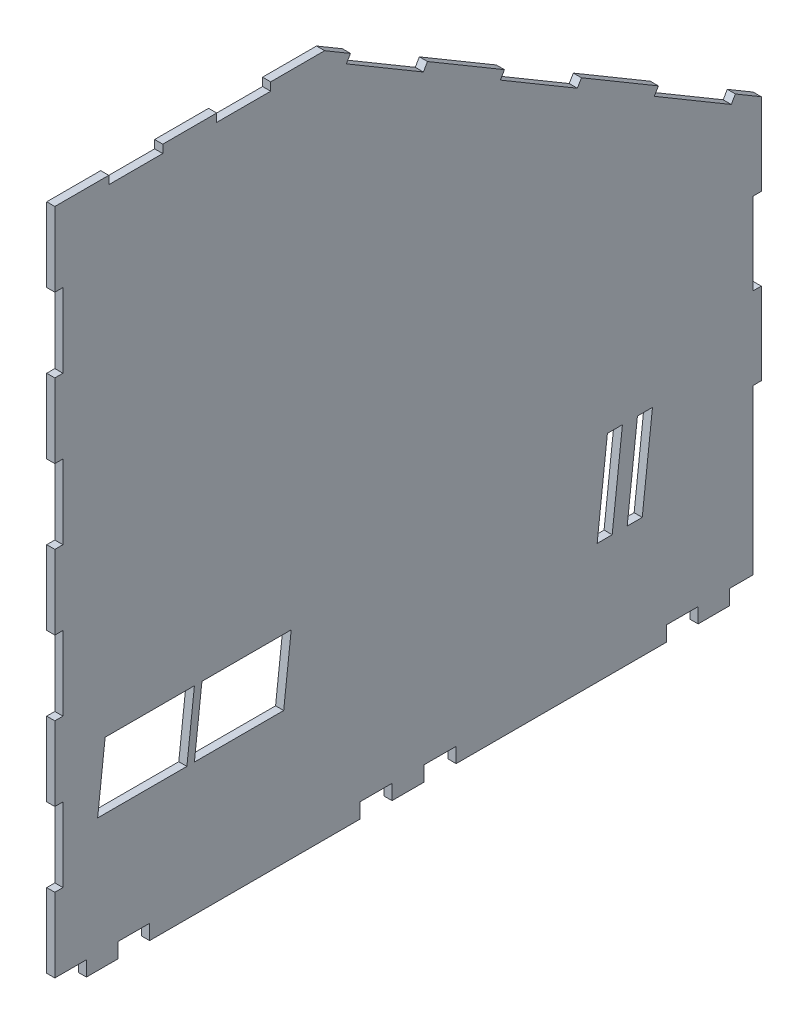
SolidWorks part; units mm, degrees
ref_plane "Ön Düzlem" through (0, 0, 0) normal (0, 0, 1) x (1, 0, 0)
ref_plane "Üst Düzlem" through (0, 0, 0) normal (0, 1, 0) x (1, 0, 0)
ref_plane "Sağ Düzlem" through (0, 0, 0) normal (1, 0, 0) x (0, 0, -1)
sketch "Sketch1" plane through (0, 0, 0) normal (1, 0, 0) x (0, 0, -1)
  line L11 (117.52, -0.68) -> (117.52, 26.6)
  line L96 (71.32, -44.8) -> (66.32, -44.8)
  line L97 (62.9109, -74.8) -> (66.32, -44.8)
  line L98 (67.9109, -74.8) -> (71.32, -44.8)
  line L99 (72.9109, -74.8) -> (76.32, -44.8)
  line L100 (77.9109, -74.8) -> (81.32, -44.8)
  line L101 (76.32, -44.8) -> (81.32, -44.8)
  line L102 (-68.58, -48.8) -> (-41.38, -48.8)
  line L103 (-71.08, -70.8) -> (-41.38, -70.8)
  line L104 (-100.78, -48.8) -> (-103.28, -70.8)
  line L105 (-100.78, -70.8) -> (-103.28, -70.8)
  line L106 (-38.88, -48.8) -> (-41.38, -70.8)
  line L107 (-41.38, -48.8) -> (-38.88, -48.8)
  line L108 (-71.08, -48.8) -> (-73.58, -70.8)
  line L109 (-68.58, -48.8) -> (-71.08, -70.8)
  line L110 (-100.78, -70.8) -> (-73.58, -70.8)
  line L111 (-100.78, -48.8) -> (-71.08, -48.8)
  line L112 (62.9109, -74.8) -> (67.9109, -74.8)
  line L113 (77.9109, -74.8) -> (72.9109, -74.8)
  line L114 (114.82, -82.52) -> (114.82, -109.8)
  line L115 (-81.612, 112.5) -> (-63.658, 112.5)
  line L116 (-45.704, 112.5) -> (-27.75, 112.5)
  line L117 (81.9271, 44.5098) -> (83.3014, 46.8339)
  line L118 (56.3162, 59.6539) -> (57.6905, 61.978)
  line L119 (30.7053, 74.7979) -> (32.0795, 77.122)
  line L120 (5.0944, 89.942) -> (-20.5165, 105.086)
  line L121 (56.3162, 59.6539) -> (30.7053, 74.7979)
  line L122 (-19.1423, 107.4101) -> (-20.5165, 105.086)
  line L123 (108.9123, 31.6899) -> (107.538, 29.3658)
  line L124 (-86, -114.8) -> (-86, -112.5)
  line L125 (-16, -114.8) -> (-86, -114.8)
  line L126 (-99.566, 109.8) -> (-99.566, 112.5)
  line L127 (-81.612, 109.8) -> (-81.612, 112.5)
  line L128 (-63.658, 109.8) -> (-63.658, 112.5)
  line L129 (-45.704, 109.8) -> (-45.704, 112.5)
  line L130 (108.9123, 31.6899) -> (117.52, 26.6)
  line L131 (-63.658, 109.8) -> (-45.704, 109.8)
  line L132 (-16, -112.5) -> (-16, -114.8)
  line L133 (-99.566, 109.8) -> (-81.612, 109.8)
  line L134 (16, -114.8) -> (16, -112.5)
  line L135 (107.538, 29.3658) -> (81.9271, 44.5098)
  line L136 (5.0944, 89.942) -> (6.4686, 92.2661)
  line L137 (57.6905, 61.978) -> (83.3014, 46.8339)
  line L138 (-117.52, -60.4) -> (-114.82, -60.4)
  line L139 (-117.52, -35.7) -> (-114.82, -35.7)
  line L140 (-117.52, -11) -> (-114.82, -11)
  line L141 (-117.52, 38.4) -> (-114.82, 38.4)
  line L142 (-117.52, 63.1) -> (-114.82, 63.1)
  line L143 (-117.52, 87.8) -> (-114.82, 87.8)
  line L144 (-117.52, 13.7) -> (-114.82, 13.7)
  line L145 (-117.52, -85.1) -> (-114.82, -85.1)
  line L146 (-114.82, -85.1) -> (-114.82, -60.4)
  line L147 (-117.52, 87.8) -> (-117.52, 112.5)
  line L148 (-107.0133, -112.5) -> (-107.0133, -114.8)
  line L149 (-117.52, 38.4) -> (-117.52, 63.1)
  line L150 (-114.82, 63.1) -> (-114.82, 87.8)
  line L151 (-117.52, -11) -> (-117.52, 13.7)
  line L152 (-114.82, 13.7) -> (-114.82, 38.4)
  line L153 (-117.52, -60.4) -> (-117.52, -35.7)
  line L154 (-107.0133, -109.8) -> (-117.52, -109.8)
  line L155 (-107.0133, -109.8) -> (-107.0133, -112.5)
  line L156 (-96.5067, -109.8) -> (-96.5067, -112.5)
  line L157 (-86, -109.8) -> (-86, -112.5)
  line L158 (-96.5067, -114.8) -> (-107.0133, -114.8)
  line L159 (-86, -109.8) -> (-96.5067, -109.8)
  line L160 (-114.82, -35.7) -> (-114.82, -11)
  line L161 (-96.5067, -112.5) -> (-96.5067, -114.8)
  line L162 (-5.3333, -114.8) -> (-5.3333, -112.5)
  line L163 (-16, -109.8) -> (-16, -112.5)
  line L164 (-5.3333, -109.8) -> (-5.3333, -112.5)
  line L165 (5.3333, -109.8) -> (5.3333, -112.5)
  line L166 (-5.3333, -109.8) -> (-16, -109.8)
  line L167 (86, -114.8) -> (16, -114.8)
  line L168 (5.3333, -114.8) -> (-5.3333, -114.8)
  line L169 (16, -109.8) -> (5.3333, -109.8)
  line L170 (16, -112.5) -> (16, -109.8)
  line L171 (5.3333, -112.5) -> (5.3333, -114.8)
  line L172 (96.5067, -109.8) -> (86, -109.8)
  line L173 (96.5067, -109.8) -> (96.5067, -112.5)
  line L174 (107.0133, -109.8) -> (107.0133, -112.5)
  line L175 (86, -109.8) -> (86, -112.5)
  line L176 (117.52, -55.24) -> (114.82, -55.24)
  line L177 (114.82, -82.52) -> (114.82, -55.24)
  line L178 (117.52, -27.96) -> (114.82, -27.96)
  line L179 (117.52, -0.68) -> (114.82, -0.68)
  line L180 (96.5067, -114.8) -> (96.5067, -112.5)
  line L181 (117.52, -55.24) -> (117.52, -27.96)
  line L182 (114.82, -27.96) -> (114.82, -0.68)
  line L183 (86, -112.5) -> (86, -114.8)
  line L184 (107.0133, -114.8) -> (96.5067, -114.8)
  line L185 (114.82, -109.8) -> (107.0133, -109.8)
  line L186 (-27.75, 112.5) -> (-19.1423, 107.4101)
  line L187 (6.4686, 92.2661) -> (32.0795, 77.122)
  line L188 (107.0133, -112.5) -> (107.0133, -114.8)
  line L189 (-117.52, -109.8) -> (-117.52, -85.1)
  line L190 (-117.52, 112.5) -> (-99.566, 112.5)
  point P287 (0, 0)
extrude "Boss-Extrude1" add sketch "Sketch1" along normal blind 2.7
